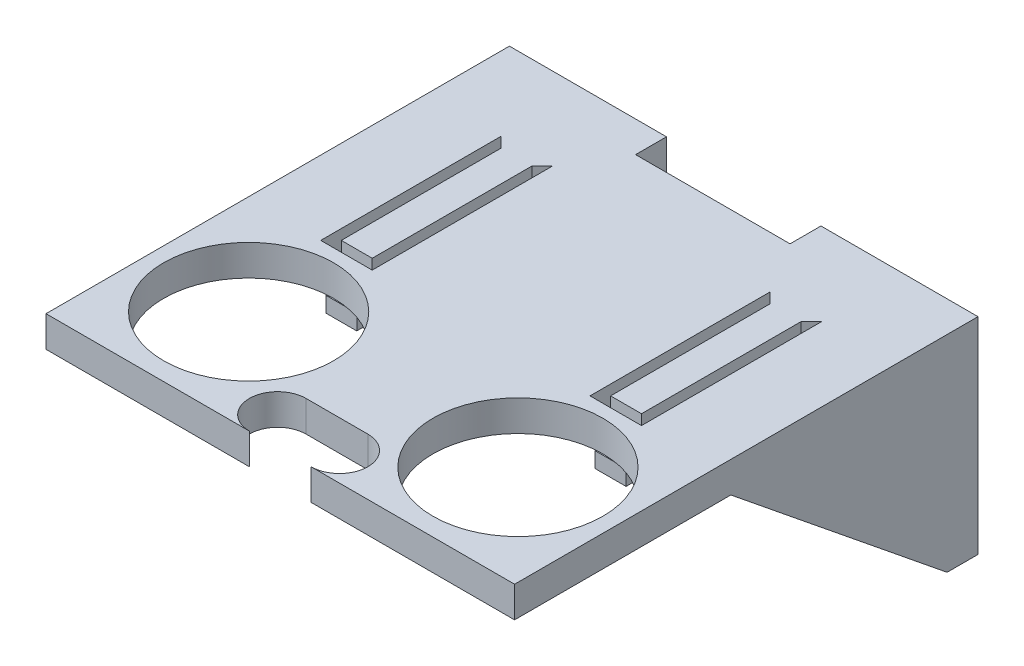
SolidWorks part; units mm, degrees
ref_plane "Front" through (0, 0, 0) normal (0, 0, 1) x (1, 0, 0)
ref_plane "Top" through (0, 0, 0) normal (0, 1, 0) x (1, 0, 0)
ref_plane "Right" through (0, 0, 0) normal (1, 0, 0) x (0, 0, -1)
sketch "Sketch1" plane through (0, 0, 0) normal (0, 0, 1) x (1, 0, 0)
  line L0 (-21.3496, -3.9653) -> (-21.3496, 16.0347)
  line L1 (-36.5996, 16.0347) -> (8.9004, 16.0347)
  line L2 (-36.5996, 16.0347) -> (-36.5996, -3.9653)
  line L3 (-36.5996, -3.9653) -> (8.9004, -3.9653)
  line L4 (8.9004, 16.0347) -> (8.9004, -3.9653)
  line L5 (-6.3496, -3.9653) -> (-6.3496, 16.0347)
  circle A0 centre (-29.5996, 6.0347) radius 2.25
  circle A1 centre (1.9004, 6.0347) radius 2.25
  point P12 (-13.8496, 16.0347)
  dimension "D3" = 4.5
  dimension "D4" = 4.5
  dimension "D5" = 7
  dimension "D6" = 7
  dimension "D7" = 10
  dimension "D8" = 10
  dimension "D1" = 45.5
  dimension "D2" = 20
  dimension "D9" = 7.5
  dimension "D10" = 7.5
extrude "Boss-Extrude1" add sketch "Sketch1" along normal blind 3 contours L2 L3 L0 L1 A0 | L5 L3 L4 L1 A1 region at (-28.9746, -3.7138, 0) region at (-6.0981, 6.0347, 0)
sketch "Sketch2" plane through (0, 0, 3) normal (0, 0, 1) x (1, 0, 0)
  line L1 (-36.5996, 16.0347) -> (8.9004, 16.0347)
  line L2 (-36.5996, 16.0347) -> (-36.5996, 13.0347)
  line L3 (-36.5996, 13.0347) -> (8.9004, 13.0347)
  line L4 (8.9004, 16.0347) -> (8.9004, 13.0347)
  line L5 (8.9004, 16.0347) -> (8.9004, -3.9653) construction
  dimension "D1" = 3
extrude "Boss-Extrude2" add sketch "Sketch2" along normal blind 42 contours L3 L4 L1 L2
sketch "Sketch3" plane through (0, 13.0347, 0) normal (0, -1, 0) x (-1, 0, 0)
  line L0 (36.5996, -45) -> (-8.9004, -45) construction
  line L1 (18.6746, -35) -> (9.0246, -35)
  circle A0 centre (26.9246, -35) radius 8.25
  circle A1 centre (0.7746, -35) radius 8.25
  point P8 (13.8496, -35)
  point P9 (13.8496, -45)
  dimension "D1" = 16.5
  dimension "D2" = 16.5
  dimension "D3" = 10
  dimension "D4" = 10
  dimension "D5" = 26.15
extrude "Cut-Extrude1" cut sketch "Sketch3" against normal through all contours A0 | A1 region at (-0.7746, 13.0347, 35) region at (-26.9246, 13.0347, 35)
sketch "Sketch4" plane through (8.9004, 0, 0) normal (1, 0, 0) x (0, 0, -1)
  line L0 (-3, -3.9653) -> (-24, 13.0347)
  line L1 (-45, 13.0347) -> (-3, 13.0347) construction
  line L2 (-24, 13.0347) -> (-3, 13.0347)
  line L3 (-3, 16.0347) -> (-3, -3.9653) construction
  line L4 (-3, 13.0347) -> (-3, -3.9653)
  dimension "D1" = 21
extrude "Boss-Extrude3" add sketch "Sketch4" against normal blind 2
pattern_linear "LPattern1" count 2 spacing 43.5 along (-1, 0, 0) of "Boss-Extrude3"
sketch "Sketch5" plane through (0, 13.0347, 0) normal (0, -1, 0) x (-1, 0, 0)
  line L0 (29.4246, -8) -> (29.4246, -25.5)
  line L1 (29.4246, -25.5) -> (24.4246, -25.5)
  line L2 (24.4246, -25.5) -> (24.4246, -8)
  line L3 (24.4246, -8) -> (25.4246, -8)
  line L4 (25.4246, -8) -> (25.4246, -24.5)
  line L5 (25.4246, -24.5) -> (28.4246, -24.5)
  line L6 (28.4246, -24.5) -> (28.4246, -8)
  line L7 (28.4246, -8) -> (29.4246, -8)
  line L8 (36.5996, -45) -> (-8.9004, -45) construction
  line L9 (34.5996, -3) -> (21.3496, -3) construction
  line L11 (13.8496, -45) -> (13.8496, -32.1492)
  line L12 (-0.7254, -8) -> (-1.7254, -8)
  line L13 (-0.7254, -24.5) -> (-0.7254, -8)
  line L14 (2.2746, -24.5) -> (-0.7254, -24.5)
  line L15 (2.2746, -8) -> (2.2746, -24.5)
  line L16 (3.2746, -8) -> (2.2746, -8)
  line L17 (3.2746, -25.5) -> (3.2746, -8)
  line L18 (-1.7254, -25.5) -> (3.2746, -25.5)
  line L19 (-1.7254, -8) -> (-1.7254, -25.5)
  point P2 (26.9246, -25.5)
  point P9 (0.7746, -35)
  point P11 (26.9246, -35)
  point P17 (13.8496, -45)
  point P28 (0.7746, -25.5)
  dimension "D1" = 1
  dimension "D2" = 1
  dimension "D3" = 3
  dimension "D4" = 1
  dimension "D5" = 19.5
  dimension "D6" = 5
extrude "Cut-Extrude2" cut sketch "Sketch5" against normal through all contours L0 L1 L2 L3 L4 L5 L6 L7 | L17 L16 L15 L14 L13 L12 L19 L18
sketch "Sketch6" plane through (-25.4246, 0, 0) normal (1, 0, 0) x (0, 0, -1)
  line L1 (-24.5, 13.0347) -> (-26, 12.1687)
  line L2 (-26, 12.1687) -> (-26, 10.6687)
  line L3 (-26, 10.6687) -> (-21.5, 10.6687)
  line L4 (-21.5, 10.6687) -> (-19.134, 13.0347)
  line L5 (-8, 13.0347) -> (-24.5, 13.0347) construction
  line L6 (-19.134, 13.0347) -> (-24.5, 13.0347)
  dimension "D1" = 45
  dimension "D2" = 3
  dimension "D3" = 1.5
  dimension "D4" = 60
  dimension "D5" = 1.5
extrude "Boss-Extrude4" add sketch "Sketch6" against normal blind 3
sketch "Sketch8" plane through (0, 13.0347, 0) normal (0, -1, 0) x (-1, 0, 0)
  line L0 (25.4246, -8) -> (2.2746, -8)
  point P4 (13.8496, -8)
  dimension "D1" = 23.15
ref_plane "Plane5" through (-13.8496, 13.0347, 8) normal (1, 0, 0) x (0, 0, -1)
mirror "Mirror7" about plane through (-13.8496, 13.0347, 8) normal (1, 0, 0) of "Boss-Extrude4"
sketch "Sketch9" plane through (0, 13.0347, 0) normal (0, -1, 0) x (-1, 0, 0)
  line L0 (16.8496, -45) -> (10.8496, -45)
  line L1 (16.8496, -39.5) -> (10.8496, -39.5)
  line L2 (36.5996, -45) -> (-8.9004, -45) construction
  arc A0 (16.8496, -45) -> (16.8496, -39.5) centre (16.8496, -42.25) ccw
  arc A1 (10.8496, -45) -> (10.8496, -39.5) centre (10.8496, -42.25) cw
  point P8 (13.8496, -45)
  point P9 (13.8496, -45)
  dimension "D2" = 6
  dimension "D1" = 5.5
extrude "Cut-Extrude3" cut sketch "Sketch9" against normal through all
sketch "Sketch10" plane through (0, 13.0347, 0) normal (0, -1, 0) x (-1, 0, 0)
  line L0 (10.8496, -39.5) -> (16.8496, -39.5) construction
  line L1 (8.8496, -27.5) -> (18.8496, -27.5)
  line L2 (8.8496, -27.5) -> (8.8496, -25)
  line L3 (8.8496, -25) -> (18.8496, -25)
  line L4 (18.8496, -27.5) -> (18.8496, -25)
  line L5 (36.5996, -45) -> (16.8496, -45) construction
  point P4 (13.8496, -27.5)
  point P9 (13.8496, -39.5)
  dimension "D1" = 10
  dimension "D2" = 2.5
  dimension "D3" = 20
extrude "Cut-Extrude4" cut sketch "Sketch10" against normal blind 2 contours L1 L4 L3 L2
sketch "Sketch11" plane through (-34.5996, 0, 0) normal (1, 0, 0) x (0, 0, -1)
  line L0 (-3, -3.9653) -> (-3, -0.4653)
  line L3 (-3, -3.9653) -> (-3, 13.0347) construction
  line L4 (-3, -0.4653) -> (-4.5, -0.4653)
  line L5 (-4.5, -0.4653) -> (-5.6178, -1.8461)
  line L6 (-24, 13.0347) -> (-3, -3.9653) construction
  line L7 (-5.6178, -1.8461) -> (-3, -3.9653)
  line L8 (-4.5, -0.4653) -> (-3, 1.3877)
  line L9 (-3, 1.3877) -> (-3, -0.4653)
  line M1 (-3, -3.9653) -> (-3, 13.0347)
  line M3 (-24, 13.0347) -> (-3, -3.9653)
  dimension "D1" = 1.5
  dimension "D2" = 3.5
extrude "Boss-Extrude5" add sketch "Sketch11" along normal up to surface (41.5 mm away) contours L4 L5 M3 M1 region at (-34.5996, -1.8771, 3.9648) up to face at (6.9004, 7.3681, 10)
sketch "Sketch13" plane through (0, 13.0347, 0) normal (0, -1, 0) x (-1, 0, 0)
  line L1 (28.4246, -19.134) -> (25.4246, -19.134)
  line L2 (28.4246, -19.134) -> (28.4246, -8)
  line L3 (28.4246, -8) -> (25.4246, -8)
  line L4 (25.4246, -19.134) -> (25.4246, -8)
  line L5 (2.2746, -19.134) -> (-0.7254, -19.134)
  line L6 (2.2746, -19.134) -> (2.2746, -8)
  line L7 (2.2746, -8) -> (-0.7254, -8)
  line L8 (-0.7254, -19.134) -> (-0.7254, -8)
extrude "Cut-Extrude6" cut sketch "Sketch13" against normal blind 1
chamfer "Chamfer1" distance 1 angle 45 2 edges at (-26.9246, 14.0347, 8) (-0.7746, 14.0347, 8)
extrude "Boss-Extrude6" add sketch "Sketch11<3>" along normal offset from surface (13.25 mm away) 7.5 contours L8 L4 M1 region at (-34.5996, 0.1524, 3.5) up to plane "Plane5"
sketch "Sketch11<3>" plane through (-34.5996, 0, 0) normal (1, 0, 0) x (0, 0, -1) same geometry as "Sketch11"
mirror "Mirror8" about plane through (-13.8496, 13.0347, 8) normal (1, 0, 0) of "Boss-Extrude6"
chamfer "Chamfer2" distance 1 angle 45 4 edges at (-28.4246, 14.5347, 8) (-25.4246, 14.5347, 8) (-2.2746, 14.5347, 8) (0.7254, 14.5347, 8)
